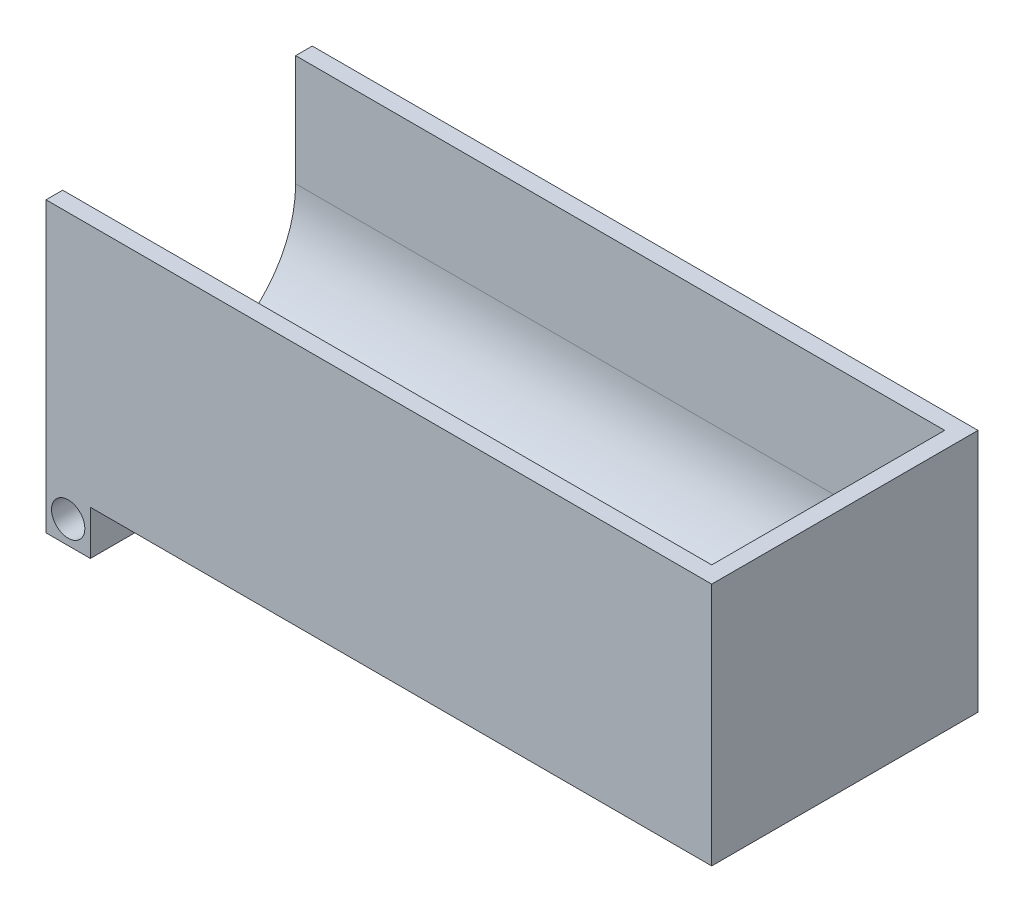
SolidWorks part; units mm, degrees
ref_plane "Front Plane" through (0, 0, 0) normal (0, 0, 1) x (1, 0, 0)
ref_plane "Top Plane" through (0, 0, 0) normal (0, 1, 0) x (1, 0, 0)
ref_plane "Right Plane" through (0, 0, 0) normal (1, 0, 0) x (0, 0, -1)
sketch "Sketch1" plane through (0, 0, 0) normal (1, 0, 0) x (0, 0, -1)
  line L0 (21, 0) -> (24, 0)
  line L1 (24, 0) -> (24, -24)
  line L2 (24, -24) -> (-24, -24)
  line L3 (-24, -24) -> (-24, 0)
  line L4 (-24, 0) -> (-21, 0)
  arc A0 (21, 0) -> (-21, 0) centre (0, 0) cw
  dimension "D3" = 21
  dimension "D1" = 3
  dimension "D2" = 3
  dimension "D4" = 24
extrude "Boss-Extrude1" add sketch "Sketch1" along normal blind 120
sketch "Sketch2" plane through (0, 0, 24) normal (0, 0, 1) x (1, 0, 0)
  line L1 (0, -24) -> (8, -24)
  line L2 (0, -24) -> (0, -32)
  line L3 (0, -32) -> (8, -32)
  line L4 (8, -24) -> (8, -32)
  dimension "D1" = 8
  dimension "D2" = 8
extrude "Boss-Extrude2" add sketch "Sketch2" against normal blind 48
sketch "Sketch3" plane through (0, 0, 24) normal (0, 0, 1) x (1, 0, 0)
  line L0 (0, -32) -> (8, -32) construction
  circle A0 centre (4, -27.8358) radius 3
  point P5 (4, -32)
  dimension "D1" = 6
extrude "Cut-Extrude1" cut sketch "Sketch3" against normal up to next
sketch "Sketch4" plane through (120, 0, 0) normal (1, 0, 0) x (0, 0, -1)
  line L1 (24, 0) -> (-24, 0)
  line L2 (24, 0) -> (24, -24)
  line L3 (24, -24) -> (-24, -24)
  line L4 (-24, 0) -> (-24, -24)
extrude "Boss-Extrude3" add sketch "Sketch4" against normal blind 3
sketch "Sketch5" plane through (0, -24, 0) normal (0, -1, 0) x (1, 0, 0)
  line L0 (120, -24) -> (8, -24) construction
  line L1 (34, -13.3) -> (28, -13.3)
  line L2 (34, -13.3) -> (34, -10.3)
  line L3 (34, -10.3) -> (28, -10.3)
  line L4 (28, -13.3) -> (28, -10.3)
  line L6 (8, -24) -> (8, 24) construction
  dimension "D1" = 10.7
  dimension "D2" = 3
  dimension "D3" = 20
  dimension "D4" = 6
extrude "Boss-Extrude4" add sketch "Sketch5" along normal blind 5
sketch "Sketch6" plane through (0, 0, -10.3) normal (0, 0, 1) x (1, 0, 0)
  line L0 (28, -29) -> (34, -29) construction
  circle A0 centre (31, -26.5) radius 0.75
  point P4 (31, -29)
  dimension "D1" = 1.5
  dimension "D2" = 2.5
extrude "Cut-Extrude2" cut sketch "Sketch6" against normal through all
sketch "Sketch7" plane through (0, 0, 0) normal (0, 1, 0) x (1, 0, 0)
  line L8 (120, 24) -> (0, 24)
  line L9 (0, 24) -> (0, 21)
  line L10 (0, 21) -> (117, 21)
  line L11 (117, 21) -> (117, -21)
  line L12 (117, -21) -> (0, -21)
  line L13 (0, -21) -> (0, -24)
  line L14 (0, -24) -> (120, -24)
  line L15 (120, -24) -> (120, 24)
  line L16 (120, 24) -> (0, 24)
  line L17 (0, 24) -> (0, 21)
  line L18 (0, 21) -> (117, 21)
  line L19 (117, 21) -> (117, -21)
  line L20 (117, -21) -> (0, -21)
  line L21 (0, -21) -> (0, -24)
  line L22 (0, -24) -> (120, -24)
  line L23 (120, -24) -> (120, 24)
  dimension "D1" = 0
extrude "Boss-Extrude5" add sketch "Sketch7" along normal blind 20
